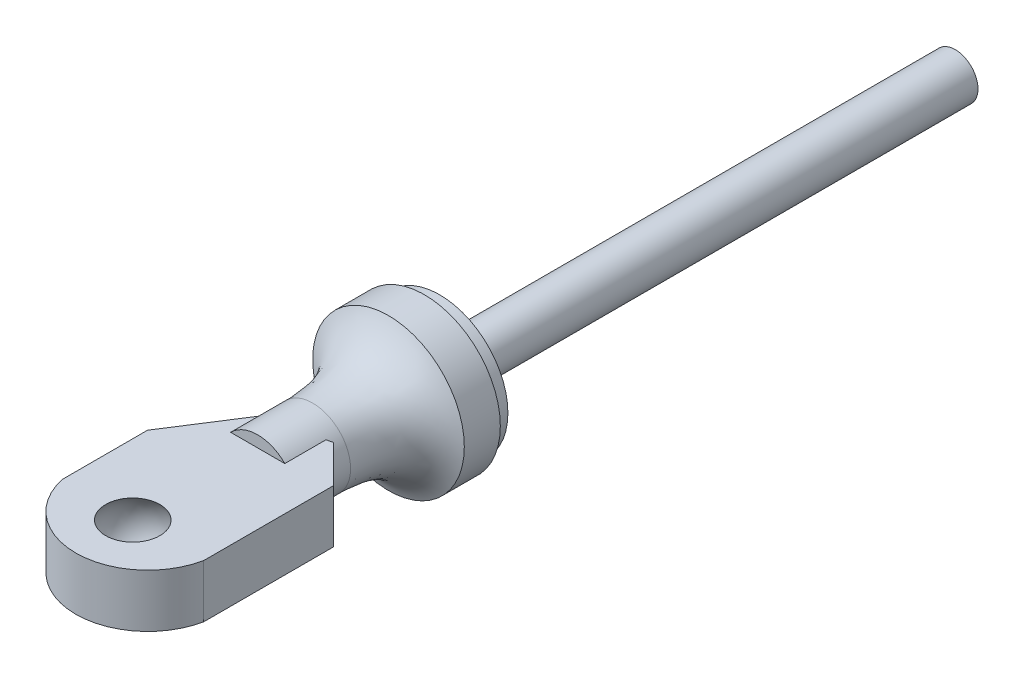
SolidWorks part; units mm, degrees
ref_plane "Front Plane" through (0, 0, 0) normal (0, 0, 1) x (1, 0, 0)
ref_plane "Top Plane" through (0, 0, 0) normal (0, 1, 0) x (1, 0, 0)
ref_plane "Right Plane" through (0, 0, 0) normal (1, 0, 0) x (0, 0, -1)
sketch "Sketch1" plane through (0, 0, 0) normal (0, 0, 1) x (1, 0, 0)
  circle A0 centre (0, 0) radius 1.5
  dimension "D1" = 3
extrude "Shaft" add sketch "Sketch1" along normal blind 34 contours A0
sketch "Sketch2" plane through (0, 0, 0) normal (1, 0, 0) x (0, 0, -1)
  line L0 (-34, 0) -> (-34, 4.5)
  line L1 (-34, 1.5) -> (-34, -1.5) construction
  line L2 (-34, 4.5) -> (-35, 4.5)
  line L3 (-35, 4.5) -> (-35, 5)
  line L4 (-35, 5) -> (-37.3747, 5)
  line L5 (-42.3747, 2.5) -> (-46, 2.5)
  line L6 (-46, 2.5) -> (-46, 0)
  line L7 (-46, 0) -> (-34, 0)
  spline S0 degree 3 poles (-37.3747, 5) (-38.2532, 3.0706) (-40.0482, 2.5) (-42.3747, 2.5) knots 0 0 0 0 1 1 1 1
  point P15 (-34.5, 4.5)
  dimension "D1" = 12
  dimension "D2" = 2.5
  dimension "D3" = 0.5
  dimension "D4" = 5
  dimension "D5" = 1
  dimension "D6" = 5
revolve "Taper" add sketch "Sketch2" angle 360 about L7
sketch "Sketch3" plane through (0, 0, 0) normal (0, 1, 0) x (1, 0, 0)
  line L0 (-4.6459, -44.6887) -> (-4.6459, -54.2392)
  line L1 (-2.5, -46) -> (2.5, -46) construction
  line L2 (-4.6459, -44.6887) -> (4.6516, -42.6529)
  line L3 (4.6516, -42.6529) -> (4.6516, -54.2116)
  arc A0 (-4.6459, -54.2392) -> (4.6516, -54.2116) centre (0, -53.25) ccw
  point P10 (0.0141, -58)
  dimension "D1" = 4.75
  dimension "D2" = 14
  dimension "D3" = 12
extrude "Ball Stick" add sketch "Sketch3" along normal mid plane 3.5
chamfer "Stick Chamfer" distance 3 angle 45 2 edges at (4.6516, 0, 42.6529) (-4.6459, 0, 44.6887) first distance on face at (4.6516, 0, 48.4323) first distance on face at (-3.3943, 0, 44.4146)
sketch "Sketch4" plane through (0, 0, 0) normal (1, 0, 0) x (0, 0, -1)
  line L0 (-54.2392, -1.75) -> (-54.2392, 1.75)
  line L1 (-54.2392, 1.75) -> (-56.0245, 1.75)
  line L2 (-54.2116, 1.75) -> (-58, 1.75) construction
  line L3 (-54.2392, -1.75) -> (-56.0245, -1.75)
  line L4 (-58, -1.75) -> (-54.2116, -1.75) construction
  arc A0 (-56.0245, -1.75) -> (-56.0245, 1.75) centre (-54.2392, 0) cw
  dimension "D1" = 2.5
revolve "Ball Hole" cut sketch "Sketch4" angle 360 about L0
